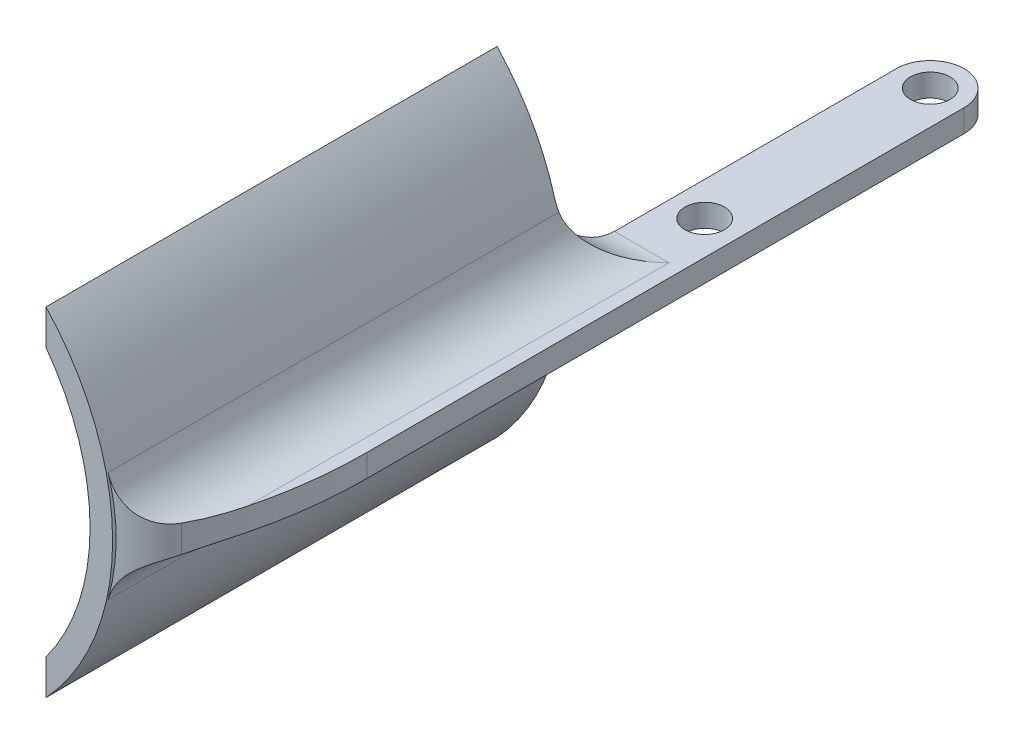
SolidWorks part; units mm, degrees
ref_plane "Front Plane" through (0, 0, 0) normal (0, 0, 1) x (1, 0, 0)
ref_plane "Top Plane" through (0, 0, 0) normal (0, 1, 0) x (1, 0, 0)
ref_plane "Right Plane" through (0, 0, 0) normal (1, 0, 0) x (0, 0, -1)
sketch "Sketch1" plane through (0, 0, 0) normal (0, 1, 0) x (1, 0, 0)
  line L0 (0, 0) -> (0, 40)
  line L1 (0, 40) -> (1.5, 40)
  line L2 (1.5, 40) -> (1.5, 70)
  line L4 (7.5, 70) -> (7.5, 17.0462)
  line L5 (3.5, 0) -> (0, 0)
  arc A0 (7.5, 17.0462) -> (3.5, 0) centre (-30.8214, 17.0462) cw
  arc A1 (1.5, 70) -> (7.5, 70) centre (4.5, 70) cw
  dimension "D2" = 40
  dimension "D4" = 6
extrude "Boss-Extrude1" add sketch "Sketch1" along normal blind 2
fillet "Fillet1" radius 10 1 edges at (1.5, 1, -40)
fillet "Fillet2" radius 5 1 edges at (3.5, 1, 0)
sketch "Sketch2" plane through (0, 2, 0) normal (0, 1, 0) x (1, 0, 0)
  line L0 (4.5, 75.6664) -> (4.5, -4.2509) construction
  circle A0 centre (4.5, 70) radius 1.75
  circle A1 centre (4.5, 50) radius 1.75
  dimension "D1" = 3.5
  dimension "D2" = 20
extrude "Cut-Extrude1" cut sketch "Sketch2" against normal through all both and the other way through all
sketch "Sketch3" plane through (0, 0, 0) normal (0, 0, 1) x (1, 0, 0)
  line L0 (10.5795, 1) -> (-44.115, 1) construction
  line L1 (0.2464, 0) -> (4.9082, 0) construction
  line L3 (-3.9065, 16) -> (-6.7712, 16)
  line L4 (-3.9065, -14) -> (-6.7712, -14)
  line L5 (0, 2) -> (0, 0) construction
  arc A0 (-6.7712, -14) -> (-6.7712, 16) centre (-20, 1) ccw
  arc A1 (-3.9065, -14) -> (-3.9065, 16) centre (-20, 1) ccw
  dimension "D2" = 40
  dimension "D3" = 2
  dimension "D1" = 1
  dimension "D4" = 30
extrude "Boss-Extrude2" add sketch "Sketch3" against normal blind 40
sketch "Sketch4" plane through (0, 0, 0) normal (0, 0, 1) x (1, 0, 0)
  line L1 (-17.2145, -15.9504) -> (-3.9065, -15.9504)
  line L2 (-17.2145, -15.9504) -> (-17.2145, 17.34)
  line L3 (-17.2145, 17.34) -> (-3.9065, 17.34)
  line L4 (-3.9065, -15.9504) -> (-3.9065, 17.34)
extrude "Cut-Extrude2" cut sketch "Sketch4" against normal through all both and the other way through all
fillet "Fillet3" radius 5 2 edges at (1.9773, 0, -20.1546) (1.9773, 2, -20.1546)
fillet "Fillet4" radius 5 2 edges at (3.1624, 0, -40) (3.1624, 2, -40)
